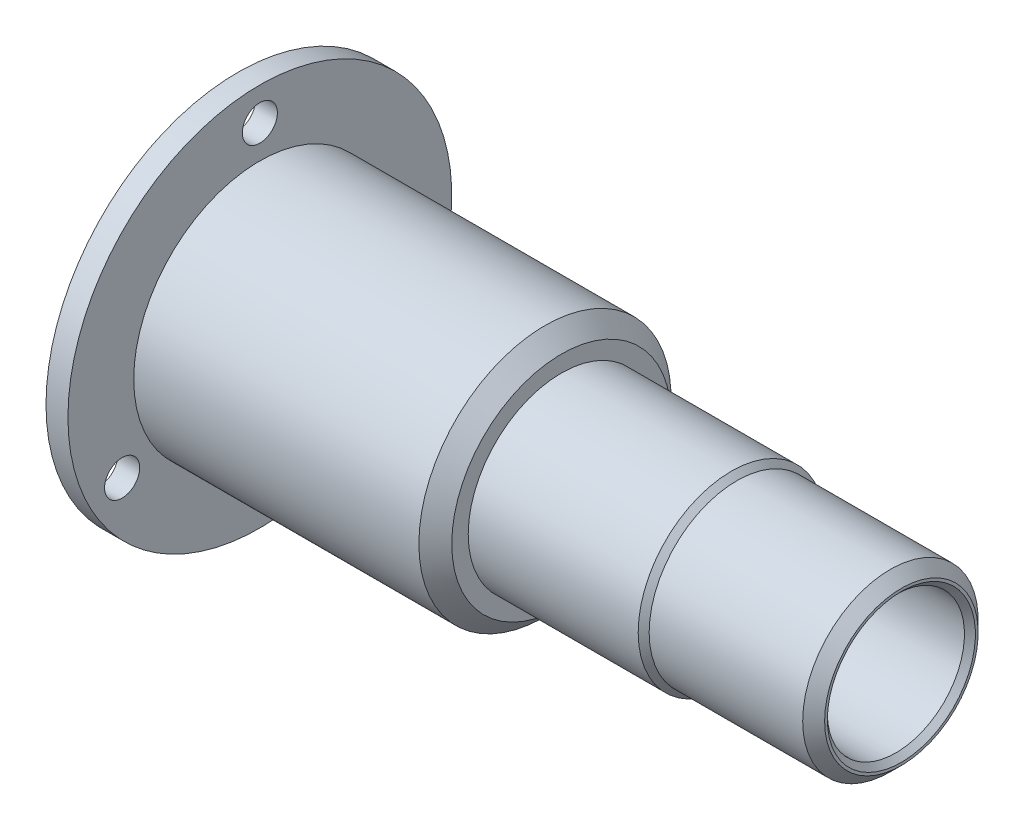
SolidWorks part; units mm, degrees
material "Сталь 45 ГОСТ 535-88"
ref_plane "Спереди" through (0, 0, 0) normal (0, 0, 1) x (1, 0, 0)
ref_plane "Сверху" through (0, 0, 0) normal (0, 1, 0) x (1, 0, 0)
ref_plane "Справа" through (0, 0, 0) normal (1, 0, 0) x (0, 0, -1)
sketch "Эскиз1" plane through (0, 0, 0) normal (0, 0, 1) x (1, 0, 0)
  line L0 (26.5, 6.25) -> (26.5, 9)
  line L1 (0, 0) -> (60.5, 0) construction
  line L2 (0, 9) -> (0, 17.5)
  line L3 (0, 17.5) -> (2, 17.5)
  line L4 (60.5, 6.25) -> (60.5, 8)
  line L5 (2, 11.5) -> (29.5, 11.5)
  line L6 (29.5, 11.5) -> (29.5, 8.5)
  line L7 (60.5, 6.25) -> (26.5, 6.25)
  line L8 (2, 11.5) -> (2, 17.5)
  line L11 (26.5, 9) -> (0, 9)
  line L13 (45.5, 8.5) -> (29.5, 8.5)
  line L17 (60.5, 8) -> (45.5, 8)
  line L20 (45.5, 8) -> (45.5, 8.5)
  dimension "D1" = 18
  dimension "D2" = 17
  dimension "D3" = 2
  dimension "D4" = 60.5
  dimension "D5" = 12.5
  dimension "D6" = 15
  dimension "D7" = 16
  dimension "D8" = 35
  dimension "D9" = 27.5
  dimension "D10" = 3
  dimension "D11" = 23
  dimension "D12" = 16
revolve "Повернуть1" add sketch "Эскиз1" angle 360 about L1
cosmetic thread "Условное изображение резьбы1" parameters "D2"=15
chamfer "Фаска1" distance 1.5 angle 45 1 edges at (29.5, 0, 11.5)
chamfer "Фаска2" distance 1 angle 45 1 edges at (0, 0, 9)
chamfer "Фаска3" distance 1 angle 45 1 edges at (60.5, 0, 8)
chamfer "Фаска4" distance 0.5 angle 45 2 edges at (45.5, 0, 8.5) (60.5, 0, 6.25)
sketch "Эскиз2" plane through (0, 0, 0) normal (-1, 0, 0) x (0, 0, 1)
  circle A0 centre (0, 0) radius 14.5 construction
  circle A1 centre (0, 14.5) radius 1.6
  circle A2 centre (12.5574, -7.25) radius 1.6
  circle A3 centre (-12.5574, -7.25) radius 1.6
  point P12 (0, 0)
  dimension "D1" = 3.2
  dimension "D2" = 29
  dimension "D3" = 3
extrude "Вырез-Вытянуть1" cut sketch "Эскиз2" against normal blind 10
